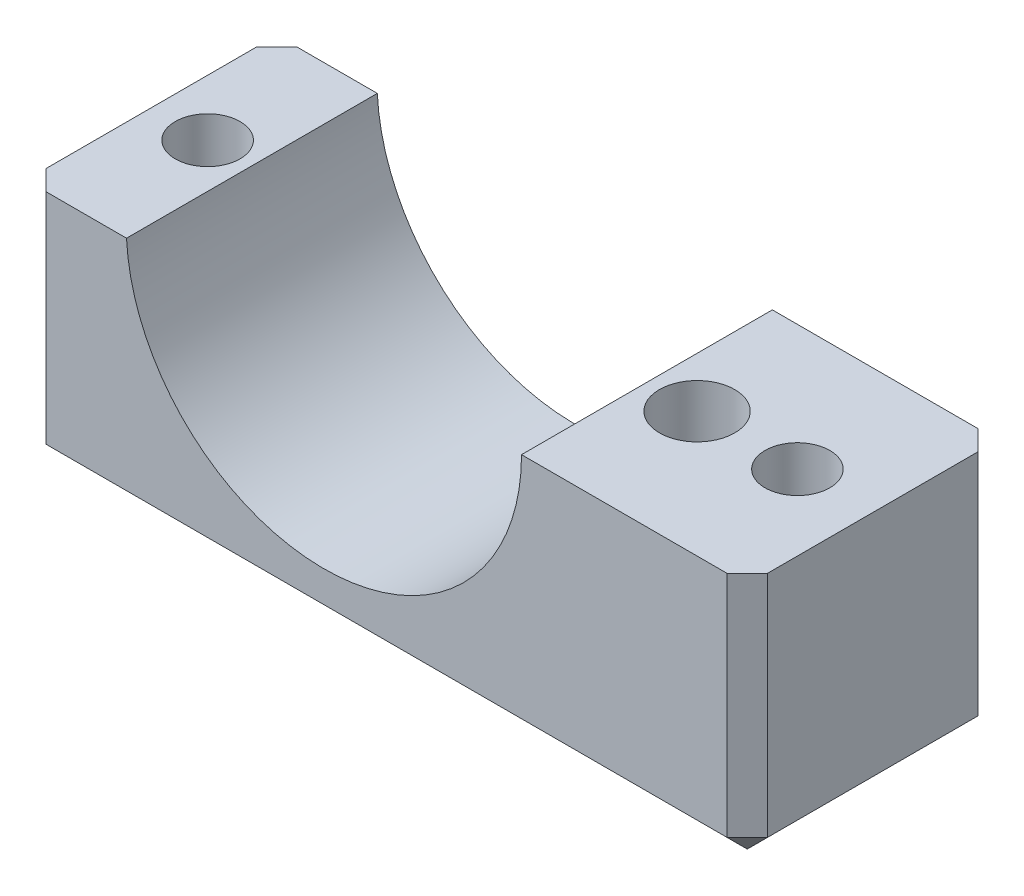
SolidWorks part; units mm, degrees
material "6061-T6 (SS)"
ref_plane "Front" through (0, 0, 0) normal (0, 0, 1) x (1, 0, 0)
ref_plane "Top" through (0, 0, 0) normal (0, 1, 0) x (1, 0, 0)
ref_plane "Right" through (0, 0, 0) normal (1, 0, 0) x (0, 0, -1)
sketch "Sketch1" plane through (0, 0, 0) normal (0, 0, 1) x (1, 0, 0)
  line L0 (0, 0) -> (12.7, 0)
  line L1 (50, 0) -> (-50, 0) construction
  line L2 (62.738, 0) -> (91.313, 0)
  line L3 (91.313, 0) -> (91.313, -31.496)
  line L4 (91.313, -31.496) -> (0, -31.496)
  line L5 (0, -50) -> (0, 50) construction
  line L6 (0, -31.496) -> (0, 0)
  arc A0 (12.7, 0) -> (62.738, 0) centre (37.719, 0) ccw
  dimension "D1" = 31.496
  dimension "D2" = 25.019
  dimension "D3" = 12.7
  dimension "D4" = 28.575
extrude "Boss-Extrude1" add sketch "Sketch1" along normal blind 31.75
sketch "Sketch2" plane through (0, -31.496, 0) normal (0, 1, 0) x (1, 0, 0)
  line L0 (12.7, -15.875) -> (7.1247, -15.875) construction
  line L1 (12.7, -31.75) -> (12.7, 0) construction
  line L2 (62.738, -15.875) -> (69.088, -15.875) construction
  line L3 (62.738, -31.75) -> (62.738, 0) construction
  line L4 (69.088, -15.875) -> (81.788, -15.875) construction
  line L5 (81.788, -15.875) -> (91.313, -15.875) construction
  line L6 (91.313, -31.75) -> (91.313, 0) construction
  line L7 (7.1247, -15.875) -> (7.1247, -25.4) construction
  line L8 (7.1247, -15.875) -> (7.1247, -6.35) construction
  line L9 (0, -31.75) -> (91.313, -31.75) construction
  dimension "D1" = 5.5753
  dimension "D2" = 6.35
  dimension "D3" = 12.7
  dimension "D4" = 6.35
hole_wizard "CBORE for 5/16 Socket Head Cap Screw1" positions "Sketch4" profile "Sketch3" counterbore size "5/16" standard "ANSI Inch" end condition through all
sketch "Sketch4" plane through (0, -31.496, 0) normal (0, -1, 0) x (-1, 0, 0)
  point P0 (-7.1247, -15.875)
  point P4 (-81.788, -15.875)
sketch "Sketch3" plane through (7.1247, -31.496, 15.875) normal (1, 0, 0) x (0, 0, -1)
  line L0 (0, 0) -> (0, 31.496)
  line L1 (0, 31.496) -> (4.1021, 31.496)
  line L3 (4.1021, 31.496) -> (4.1021, 9.525)
  line L4 (4.1021, 9.525) -> (6.35, 9.525)
  line L5 (6.35, 9.525) -> (6.35, 0)
  line L7 (6.35, 0) -> (0, 0)
  line L11 (0, -6.35) -> (0, 107.95) construction
  dimension "Thru Hole Dia." = 8.2042
  dimension "Thru Hole Depth" = 31.496
  dimension "C'Bore Dia." = 12.7
  dimension "C'Bore Depth" = 9.525
hole_wizard "3/8 (0.375) Clearance Dowel Hole2" positions "Sketch8" profile "Sketch7" hole size "3/8" standard "ANSI Inch" end condition through all
sketch "Sketch8" plane through (0, -31.496, 0) normal (0, -1, 0) x (-1, 0, 0)
  point P0 (-69.088, -15.875)
sketch "Sketch7" plane through (69.088, -31.496, 15.875) normal (1, 0, 0) x (0, 0, -1)
  line L0 (0, 0) -> (0, 31.496)
  line L1 (0, 31.496) -> (4.7625, 31.496)
  line L2 (4.7625, 31.496) -> (4.7625, 0)
  line L5 (4.7625, 0) -> (0, 0)
  line L11 (0, -6.35) -> (0, 107.95) construction
  dimension "Thru Hole Dia." = 9.525
  dimension "Thru Hole Depth" = 31.496
sketch "Sketch9" plane through (0, 0, 0) normal (0, 1, 0) x (1, 0, 0)
  line L1 (0, -31.75) -> (23.7216, -31.75)
  line L2 (0, -31.75) -> (0, 0)
  line L3 (0, 0) -> (23.7216, 0)
  line L4 (23.7216, -31.75) -> (23.7216, 0)
extrude "Cut-Extrude1" cut sketch "Sketch9" against normal blind 1.27
hole_wizard "1/4 (0.25) Clearance Dowel Hole1" [suppressed] positions "Sketch11" profile "Sketch10" hole size "1/4" standard "ANSI Inch"
sketch "Sketch11" plane through (0, -31.75, 0) normal (0, -1, 0) x (-1, 0, 0)
  point P0 (-7.1247, -25.4)
  point P3 (-7.1247, -6.35)
sketch "Sketch10" plane through (7.1247, -31.75, 25.4) normal (1, 0, 0) x (0, 0, -1)
  line L0 (0, 0) -> (0, 31.75)
  line L1 (0, 31.75) -> (3.175, 31.75)
  line L2 (3.175, 31.75) -> (3.175, 0)
  line L5 (3.175, 0) -> (0, 0)
  line L11 (0, -6.35) -> (0, 107.95) construction
  dimension "Thru Hole Dia." = 6.35
  dimension "Thru Hole Depth" = 31.75
chamfer "Chamfer1" distance 2.54 angle 45 8 edges at (91.313, -15.748, 31.75) (91.313, -15.748, 0) (91.313, -31.496, 15.875) (0, -16.383, 31.75) (45.6565, -31.496, 31.75) (0, -31.496, 15.875) (0, -16.383, 0) (45.6565, -31.496, 0)
